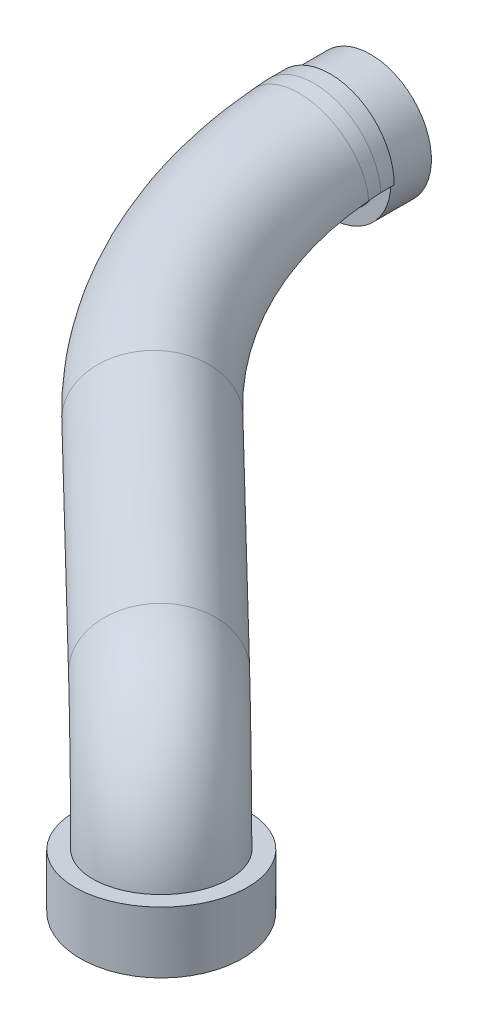
SolidWorks part; units mm, degrees
ref_plane "Front Plane" through (0, 0, 0) normal (0, 0, 1) x (1, 0, 0)
ref_plane "Top Plane" through (0, 0, 0) normal (0, 1, 0) x (1, 0, 0)
ref_plane "Right Plane" through (0, 0, 0) normal (1, 0, 0) x (0, 0, -1)
sketch3d "3DSketch3"
  line L0 (0, 0, 0) -> (0, 0, -79.5) construction
  line L1 (0, 0, -79.5) -> (0, 26, -79.5) construction
  line L2 (0, 26, -79.5) -> (-54.5, 26, -79.5) construction
  line L3 (-54.5, 26, -79.5) -> (-54.5, 26, -77.5)
  line L4 (0, 0, 0) -> (0, 1.6456, 0)
  line L5 (-54.5, 26, -77.5) -> (-54.5, 25.8458, -75.7374)
  line L6 (-54.5, 26, -79.5) -> (-54.5, -49974, -79.5) construction
  line L7 (-9.5449, 16.5449, -9.2113) -> (-37.8962, 21.1337, -36.5716)
  arc A0 (-9.5449, 16.5449, -9.2113) -> (0, 1.6456, 0) centre (-10.7936, 1.6456, -10.4163) ccw
  arc A1 (-37.8962, 21.1337, -36.5716) -> (-54.5, 25.8458, -75.7374) centre (0.3371, 21.6323, -76.106) ccw
  point P4 (0, 15, 0)
  point P8 (-0.3773, 1.6456, -21.2098)
  point P13 (-54.5, 23.8211, -52.5951)
  point P14 (-3.8924, -32.9961, -80.8854)
  dimension "D1" = 15
  dimension "D2" = 2
  dimension "D3" = 85
  dimension "D4" = 25
  dimension "D8" = 15
  dimension "D5" = 79.5
  dimension "D9" = 55
  dimension "D6" = 54.5
  dimension "D7" = 26
sketch "Sketch9" plane through (0, 0, 0) normal (0, 1, 0) x (1, 0, 0)
  circle A0 centre (0, 0) radius 7
  circle A1 centre (0, 0) radius 9.5
  dimension "D1" = 14
  dimension "D2" = 19
sweep "Sweep2" add profiles "Sketch9" path "3DSketch3"
sketch "Sketch10" plane through (0, 0, -79.5) normal (0, 0, -1) x (-1, 0, 0)
  circle A0 centre (54.5, 26) radius 7 construction
  circle A1 centre (54.5, 26) radius 7
  circle A2 centre (54.5, 26) radius 9
  dimension "D1" = 18
extrude "Boss-Extrude2" add sketch "Sketch10" along normal blind 6
sketch "Sketch13" plane through (0, 0, -79.5) normal (0, 0, -1) x (-1, 0, 0)
  line L0 (64, 26) -> (45, 26)
  arc A0 (45, 26) -> (64, 26) centre (54.5, 26) ccw
  circle A1 centre (54.5, 26) radius 9.5 construction
  point P0 (54.5, 26)
sketch3d "3DSketch4"
  line L0 (0, 0, 0) -> (0, 0, -79.5) construction
  line L1 (0, 0, -79.5) -> (0, 26, -79.5) construction
  line L2 (0, 26, -79.5) -> (-54.5, 26, -79.5) construction
  line L3 (-54.5, 26, -79.5) -> (-54.5, 26, -77.5)
  line L5 (-54.5, 26, -77.5) -> (-54.5, 25.8458, -75.7374)
  line L6 (-54.5, 23.6735, -79.5) -> (-54.5, -49976.3265, -79.5) construction
  line L7 (-9.5449, 16.5449, -9.2113) -> (-37.8962, 21.1337, -36.5716)
  arc A0 (-9.5449, 16.5449, -9.2113) -> (-0.0441, 2.9997, -0.0425) centre (-10.7936, 1.6456, -10.4163) ccw
  arc A1 (-37.8962, 21.1337, -36.5716) -> (-54.5, 25.8458, -75.7374) centre (0.3371, 21.6323, -76.106) ccw
  point P4 (0, 15, 0)
  point P8 (-0.3773, 1.6456, -21.2098)
  point P11 (-0.0441, 2.9997, -0.0425)
  point P13 (-54.5, 23.8211, -52.5951)
  point P14 (-3.8924, -32.9961, -80.8854)
  dimension "D1" = 15
  dimension "D2" = 2
  dimension "D3" = 85
  dimension "D4" = 25
  dimension "D8" = 15
  dimension "D5" = 79.5
  dimension "D10" = 3
  dimension "D9" = 55
  dimension "D6" = 54.5
  dimension "D7" = 26
sweep "Cut-Sweep4" cut profiles "Sketch13" path "3DSketch4"
sketch "Sketch14" plane through (0, 0, 0) normal (0, -1, 0) x (-1, 0, 0)
  circle A1 centre (0, 0) radius 12
  circle A4 centre (0, 0) radius 8
  point P0 (0, 0)
  dimension "D1" = 16
  dimension "D2" = 24
extrude "Boss-Extrude3" add sketch "Sketch14" against normal up to surface (2.5017 mm away) up to face at (-2.7429, 2.6287, -3.14)
sketch "Sketch15" plane through (0, 0, 0) normal (0, -1, 0) x (1, 0, 0)
  circle A0 centre (0, 0) radius 10
  circle A1 centre (0, 0) radius 12
  circle A2 centre (0, 0) radius 12 construction
  dimension "D1" = 20
extrude "Boss-Extrude4" add sketch "Sketch15" along normal blind 5
